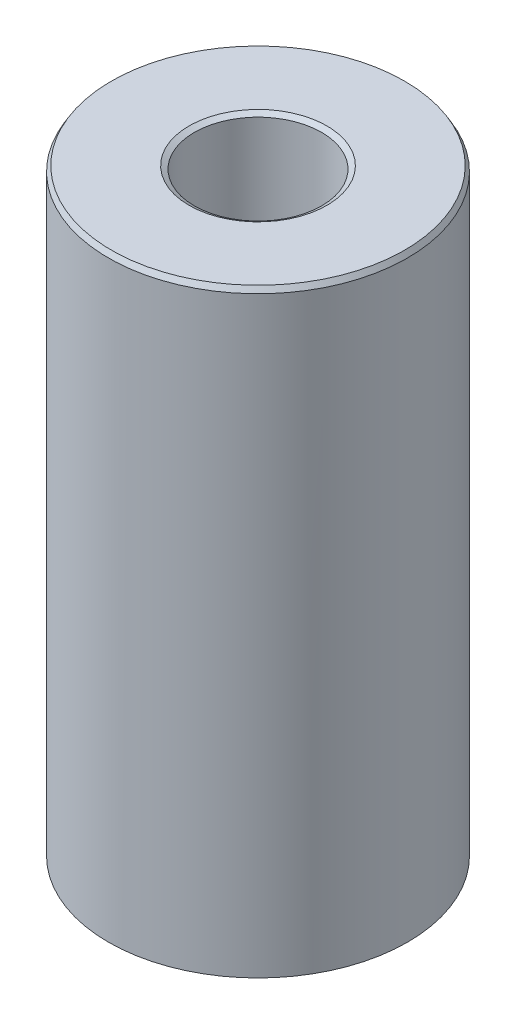
SolidWorks part; units mm, degrees
ref_plane "Front Plane" through (0, 0, 0) normal (0, 0, 1) x (1, 0, 0)
ref_plane "Top Plane" through (0, 0, 0) normal (0, 1, 0) x (1, 0, 0)
ref_plane "Right Plane" through (0, 0, 0) normal (1, 0, 0) x (0, 0, -1)
sketch "Sketch1" plane through (0, 0, 0) normal (0, 1, 0) x (1, 0, 0)
  circle A0 centre (0, 0) radius 37.5
  dimension "SLEEVE_OD" = 75
extrude "Boss-Extrude1" add sketch "Sketch1" along normal blind 150.656
sketch "Sketch2" plane through (0, 0, 0) normal (0, 1, 0) x (1, 0, 0)
  circle A0 centre (0, 0) radius 15.964
  dimension "BORE_D" = 31.9281
extrude "Cut-Extrude1" cut sketch "Sketch2" along normal through all
chamfer "Chamfer1" distance 1.3092 angle 30 4 edges at (0, 150.656, 15.964) (0, 0, 15.964) (0, 0, 37.5) (0, 150.656, 37.5) first distance on face at (0, 150.656, 15.964) first distance on face at (0, 0, 15.964) first distance on face at (0, 150.656, 37.5)
